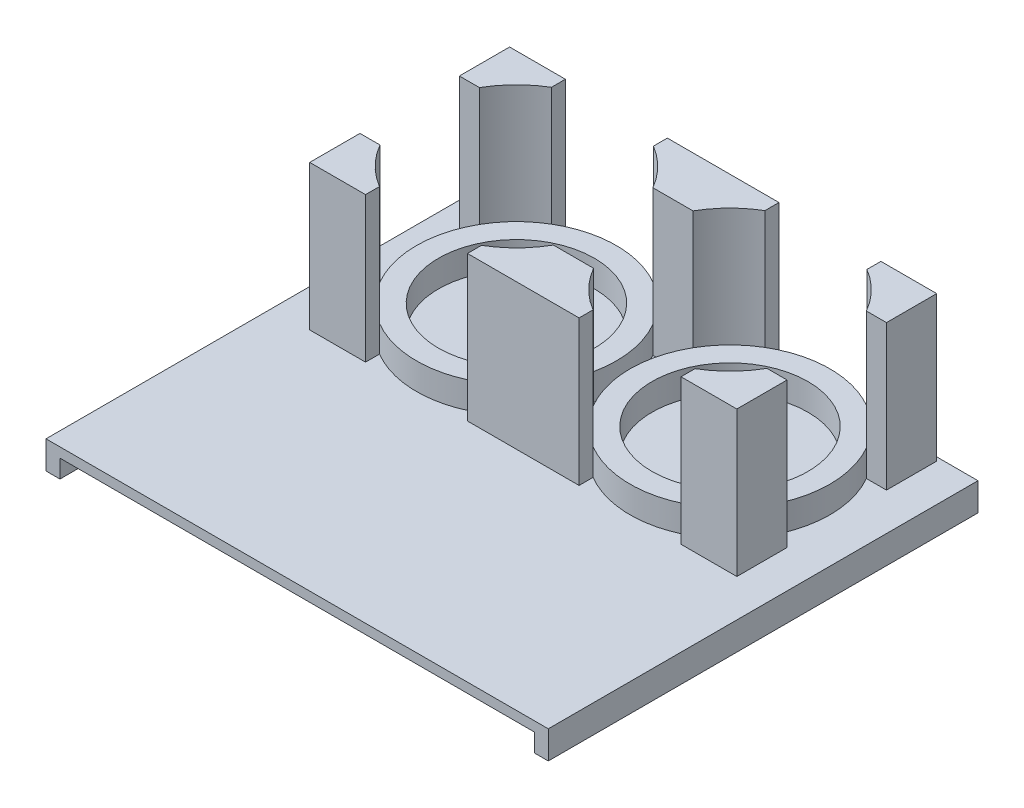
SolidWorks part; units mm, degrees
ref_plane "Front Plane" through (0, 0, 0) normal (0, 0, 1) x (1, 0, 0)
ref_plane "Top Plane" through (0, 0, 0) normal (0, 1, 0) x (1, 0, 0)
ref_plane "Right Plane" through (0, 0, 0) normal (1, 0, 0) x (0, 0, -1)
sketch "Sketch1" plane through (0, 0, 0) normal (0, 1, 0) x (1, 0, 0)
  line L0 (-42.5, 38.5) -> (42.5, 38.5)
  line L1 (0, -38.5) -> (0, 38.5) construction
  line L2 (-42.5, -38.5) -> (42.5, -38.5)
  line L3 (-42.5, 38.5) -> (-42.5, -38.5)
  line L4 (42.5, 38.5) -> (42.5, -38.5)
  point P3 (0, 38.5)
  point P7 (0, 0)
  point P11 (0, -38.5)
  dimension "D1" = 85
  dimension "D3" = 77
extrude "Boss-Extrude1" add sketch "Sketch1" along normal blind 1.75
sketch "Sketch3" plane through (0, 1.75, 0) normal (0, 1, 0) x (1, 0, 0)
  line L0 (-19.1333, 19.9281) -> (19.1333, 19.9281) construction
  line L2 (-1.263, 30.3299) -> (-0.4988, 30.3299)
  line L3 (20.6515, 40.5495) -> (-0.4988, 30.3299)
  line L5 (2.3974, 9.6528) -> (17.6152, -0.6933)
  line L6 (17.6152, -0.6933) -> (36.2329, 8.3027)
  line L7 (36.2329, 8.3027) -> (37.7511, 28.9241)
  line L8 (37.7511, 28.9241) -> (20.6515, 40.5495)
  line L9 (-19.2063, 40.6052) -> (-37.0767, 30.2034)
  line L10 (-37.0767, 30.2034) -> (-37.0037, 9.5264)
  line L11 (-37.0037, 9.5264) -> (-19.0603, -0.749)
  line L12 (-19.0603, -0.749) -> (-1.1899, 9.6528)
  line L13 (-1.1899, 9.6528) -> (-1.263, 30.3299)
  line L14 (-1.263, 30.3299) -> (-19.2063, 40.6052)
  line L15 (-1.1899, 9.6528) -> (2.3974, 9.6528)
  line L16 (0.8218, 15.0915) -> (-0.7932, -6.845) [skipped]
  circle A0 centre (19.1333, 19.9281) radius 17.907
  circle A1 centre (-19.1333, 19.9281) radius 17.907
  circle A2 centre (-19.1333, 19.9281) radius 13.97
  circle A3 centre (19.1333, 19.9281) radius 13.97
  circle A4 centre (19.1333, 19.9281) radius 17.907 construction
  circle A5 centre (-19.1333, 19.9281) radius 17.907 construction
  point P4 (0, 0)
  dimension "D1" = 35.814
  dimension "D3" = 27.94
extrude "Boss-Extrude3" add sketch "Sketch3" along normal blind 4.7625 contours A2 A1 | A3 A0 region at (-1.7328, 1.75, -19.9589) region at (20.4109, 1.75, -37.2817)
sketch "Sketch4" plane through (0, 1.75, 0) normal (0, 1, 0) x (1, 0, 0)
  line L0 (-19.1333, 37.8351) -> (19.1333, 37.8351) construction
  line L1 (0, 37.8351) -> (-10, 37.8351)
  line L2 (-10, 37.8351) -> (-10, 35.3308)
  line L3 (0, 37.8351) -> (10, 37.8351)
  line L4 (10, 37.8351) -> (10, 35.3308)
  line L5 (-1.2263, 19.9281) -> (16.6975, 19.9281) construction
  line L6 (-3.5987, 28.8351) -> (3.5987, 28.8351)
  line L7 (-3.5987, 11.0211) -> (3.5987, 11.0211)
  line L8 (10, 2.0211) -> (10, 4.5254)
  line L9 (0, 2.0211) -> (10, 2.0211)
  line L10 (-10, 2.0211) -> (-10, 4.5254)
  line L11 (0, 2.0211) -> (-10, 2.0211)
  line L12 (0, 37.8351) -> (0, 28.8351)
  line L13 (0, 11.0211) -> (0, 2.0211)
  line L14 (-19.1333, 37.8351) -> (-19.1333, 19.9281) construction
  line L15 (19.1333, 37.8351) -> (19.1333, 19.9281) construction
  line L16 (-38.2667, 11.0211) -> (-38.2667, 2.0211)
  line L17 (-38.2667, 2.0211) -> (-28.2667, 2.0211)
  line L18 (-28.2667, 2.0211) -> (-28.2667, 4.5254)
  line L19 (-38.2667, 37.8351) -> (-38.2667, 28.8351)
  line L20 (-38.2667, 37.8351) -> (-28.2667, 37.8351)
  line L21 (-28.2667, 37.8351) -> (-28.2667, 35.3308)
  line L22 (-38.2667, 28.8351) -> (-34.668, 28.8351)
  line L23 (-38.2667, 11.0211) -> (-34.668, 11.0211)
  line L24 (28.2667, 2.0211) -> (28.2667, 4.5254)
  line L25 (38.2667, 2.0211) -> (28.2667, 2.0211)
  line L26 (38.2667, 11.0211) -> (38.2667, 2.0211)
  line L27 (38.2667, 28.8351) -> (34.668, 28.8351)
  line L28 (28.2667, 37.8351) -> (28.2667, 35.3308)
  line L29 (38.2667, 37.8351) -> (28.2667, 37.8351)
  line L30 (38.2667, 37.8351) -> (38.2667, 28.8351)
  line L31 (38.2667, 11.0211) -> (34.668, 11.0211)
  circle A0 centre (-19.1333, 19.9281) radius 17.907 construction
  circle A1 centre (19.1333, 19.9281) radius 17.907 construction
  arc A2 (10, 35.3308) -> (3.5987, 28.8351) centre (19.1333, 19.9281) ccw
  circle A3 centre (-19.1333, 19.9281) radius 17.907 construction
  circle A4 centre (19.1333, 19.9281) radius 17.907 construction
  arc A5 (-3.5987, 28.8351) -> (-10, 35.3308) centre (-19.1333, 19.9281) ccw
  arc A6 (-3.5987, 11.0211) -> (-10, 4.5254) centre (-19.1333, 19.9281) cw
  arc A7 (10, 4.5254) -> (3.5987, 11.0211) centre (19.1333, 19.9281) cw
  arc A8 (-34.668, 11.0211) -> (-28.2667, 4.5254) centre (-19.1333, 19.9281) ccw
  arc A9 (-34.668, 28.8351) -> (-28.2667, 35.3308) centre (-19.1333, 19.9281) cw
  arc A10 (34.668, 11.0211) -> (28.2667, 4.5254) centre (19.1333, 19.9281) cw
  arc A11 (34.668, 28.8351) -> (28.2667, 35.3308) centre (19.1333, 19.9281) ccw
  point P0 (0, 28.8351)
  point P4 (0, 0)
  point P29 (0, 11.0211)
  circle M6 centre (19.1333, 19.9281) radius 17.907
  circle M7 centre (-19.1333, 19.9281) radius 17.907
  dimension "D3" = 9
  dimension "D2" = 10
extrude "Boss-Extrude7" add sketch "Sketch4" along normal blind 26 contours L19 L22 L21 L20 M7 | L23 L16 L17 L18 M7 | L13 L7 L10 L11 M7 | L7 L13 L9 L8 M6 | L12 L1 L2 L6 M7 | L3 L12 L6 L4 M6 | L30 L29 L28 L27 M6 | L26 L31 L24 L25 M6 region at (-4.0022, 1.75, -34.1346) region at (4.0022, 1.75, -34.1346) region at (-34.2645, 1.75, -34.1346) region at (34.2645, 1.75, -34.1346) region at (4.0022, 1.75, -5.7217) region at (-4.0022, 1.75, -5.7217) region at (-34.2645, 1.75, -5.7217) region at (34.2645, 1.75, -5.7217)
sketch "Sketch6" plane through (-42.5, 0, 0) normal (-1, 0, 0) x (0, 0, 1)
  line L0 (-38.5, 1.75) -> (-38.5, -3.25)
  line L1 (38.5, 1.75) -> (38.5, -3.25)
  line L2 (-38.5, 1.75) -> (38.5, 1.75) construction
  line L3 (-38.5, 1.75) -> (38.5, 1.75)
  line L4 (-38.5, -3.25) -> (38.5, -3.25)
  dimension "D1" = 5
extrude "Boss-Extrude8" add sketch "Sketch6" along normal blind 2.5
mirror "Mirror1" about plane through (0, 0, 0) normal (1, 0, 0) of "Boss-Extrude8"
